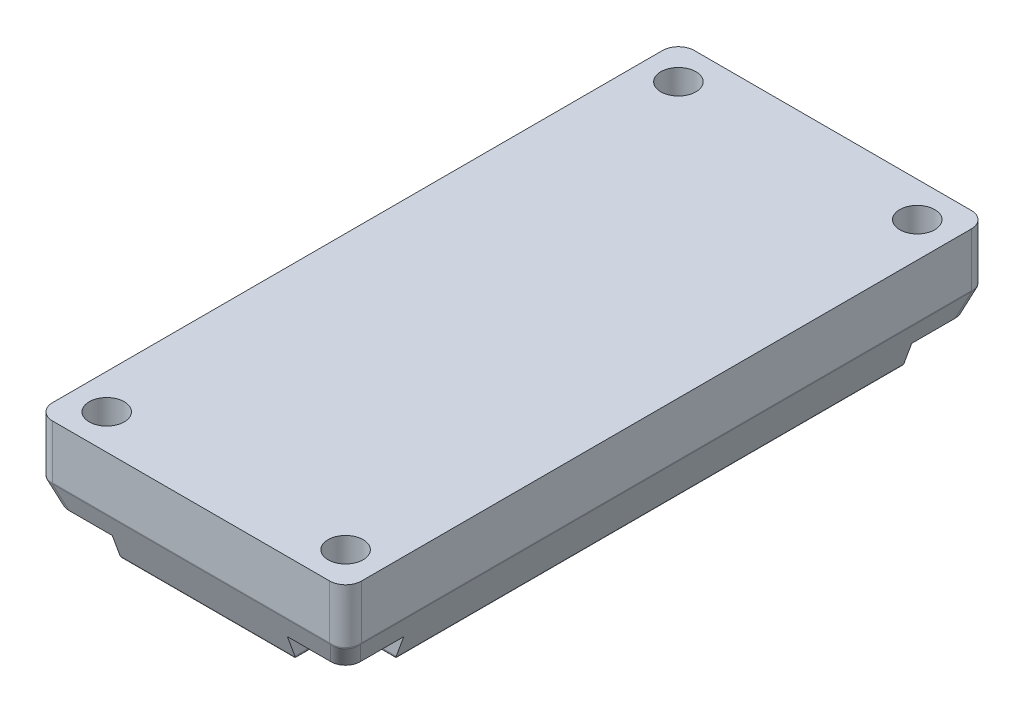
SolidWorks part; units mm, degrees
material "PC High Viscosity"
ref_plane "Front Plane" through (0, 0, 0) normal (0, 0, 1) x (1, 0, 0)
ref_plane "Top Plane" through (0, 0, 0) normal (0, 1, 0) x (1, 0, 0)
ref_plane "Right Plane" through (0, 0, 0) normal (1, 0, 0) x (0, 0, -1)
sketch "BaseS" plane through (0, 0, 0) normal (0, 1, 0) x (1, 0, 0)
  line L0 (-9.7, 20.15) -> (9.7, 20.15)
  line L1 (-9.7, 20.15) -> (-9.7, -20.15)
  line L2 (-9.7, -20.15) -> (9.7, -20.15)
  line L3 (9.7, 20.15) -> (9.7, -20.15)
  line L4 (-9.7, 20.15) -> (9.7, -20.15) construction
  line L5 (-9.7, -20.15) -> (9.7, 20.15) construction
  point P0 (0, 0)
  dimension "D1" = 19.4
  dimension "D2" = 40.3
extrude "BASE" add sketch "BaseS" along normal blind 6.4
sketch "HoleSideCutsS" plane through (0, 0, 0) normal (0, -1, 0) x (1, 0, 0)
  line L0 (-5.5, 17.75) -> (-5.5, 20.15)
  line L1 (-7.3, 15.95) -> (-9.7, 15.95)
  line L2 (-5.5, 20.15) -> (-9.7, 20.15)
  line L3 (-9.7, 20.15) -> (-9.7, 15.95)
  line L4 (-9.7, 20.15) -> (9.7, 20.15) construction
  line L5 (-9.7, -20.15) -> (-9.7, 20.15) construction
  arc A0 (-7.3, 15.95) -> (-5.5, 17.75) centre (-7.3, 17.75) ccw
  dimension "D3" = 3.6
  dimension "D1" = 4.2
extrude "HOLE SIDE CUTS" cut sketch "HoleSideCutsS" against normal blind 1.5
hole_wizard "M2 Clearance Hole1" positions "Sketch3" profile "Sketch4" hole size "M2" standard "ANSI Metric" end condition through all
sketch "Sketch3" plane through (0, 1.5, 0) normal (0, -1, 0) x (-1, 0, 0)
  line L0 (9.7, -20.15) -> (9.7, -15.95) construction
  line L1 (5.5, -20.15) -> (9.7, -20.15) construction
  point P0 (7.5, -17.95)
  dimension "D1" = 2.2
  dimension "D2" = 2.2
sketch "Sketch4" plane through (-7.5, 1.5, 17.95) normal (1, 0, 0) x (0, 0, -1)
  line L0 (0, 0) -> (0, 4.9)
  line L1 (0, 4.9) -> (1.1, 4.9)
  line L2 (1.1, 4.9) -> (1.1, 0)
  line L5 (1.1, 0) -> (0, 0)
  line L11 (0, -6.35) -> (0, 107.95) construction
  dimension "Thru Hole Dia." = 2.2
  dimension "Thru Hole Depth" = 4.9
mirror "HOLE FEATURES HM" about plane through (0, 0, 0) normal (1, 0, 0) of "M2 Clearance Hole1", "HOLE SIDE CUTS"
mirror "HOLE FEATURE VM" about plane through (0, 0, 0) normal (0, 0, 1) of "HOLE FEATURES HM", "HOLE SIDE CUTS", "M2 Clearance Hole1"
sketch "SideChamfer1S" plane through (0, 0, 0) normal (0, 0, 1) x (1, 0, 0)
  line L0 (9.7, 3) -> (9.7, 0)
  line L1 (9.7, 6.4) -> (9.7, 1.5) construction
  line L2 (9.7, 0) -> (8.6081, 0)
  line L3 (9.7, 0) -> (7.3, 0) construction
  line L4 (8.6081, 0) -> (9.7, 3)
  dimension "D1" = 3
  dimension "D2" = 20
extrude "SIDE CHAMFER 1" cut sketch "SideChamfer1S" against normal through all both and the other way through all
mirror "SC1 HM" about plane through (0, 0, 0) normal (1, 0, 0) of "SIDE CHAMFER 1"
sketch "SideChamfer2S" plane through (0, 0, 0) normal (1, 0, 0) x (0, 0, -1)
  line L0 (20.15, 3) -> (20.15, 0)
  line L1 (20.15, 6.4) -> (20.15, 3) construction
  line L2 (20.15, 0) -> (19.0581, 0)
  line L4 (19.0581, 0) -> (20.15, 3)
  dimension "D1" = 3
  dimension "D2" = 20
extrude "SIDE CHAMFER 2" cut sketch "SideChamfer2S" against normal through all both and the other way through all
mirror "SC2 VM" about plane through (0, 0, 0) normal (0, 0, 1) of "SIDE CHAMFER 2"
fillet "BASE F" radius 1 8 edges at (-9.427, 2.25, -19.877) (-9.7, 4.7, -20.15) (9.427, 2.25, -19.877) (9.7, 4.7, -20.15) (-9.427, 2.25, 19.877) (-9.7, 4.7, 20.15) (9.427, 2.25, 19.877) (9.7, 4.7, 20.15)
fillet "BASE BOTTOM F" radius 0.2 32 edges at (9.6996, 2.9988, -19.1793) (9.4071, 2.9341, -19.8571) (8.7293, 2.9988, -20.1496) (0, 3, -20.15) (-8.7293, 2.9988, -20.1496) (-9.4071, 2.9341, -19.8571) (-9.6996, 2.9988, -19.1793) (-9.7, 3, 0) (-9.6996, 2.9988, 19.1793) (-9.4071, 2.9341, 19.8571) (-8.7293, 2.9988, 20.1496) (0, 3, 20.15) (8.7293, 2.9988, 20.1496) (9.4071, 2.9341, 19.8571) (9.6996, 2.9988, 19.1793) (5.5, 0, 18.404) (6.0272, 0, 16.4772) (7.954, 0, 15.95) (8.6081, 0, 0) (7.954, 0, -15.95) (6.0272, 0, -16.4772) (5.5, 0, -18.404) (0, 0, -19.0581) (-5.5, 0, -18.404) (-6.0272, 0, -16.4772) (-7.954, 0, -15.95) (-8.6081, 0, 0) (-7.954, 0, 15.95) (-6.0272, 0, 16.4772) (-5.5, 0, 18.404) (0, 0, 19.0581) (9.7, 3, 0)
